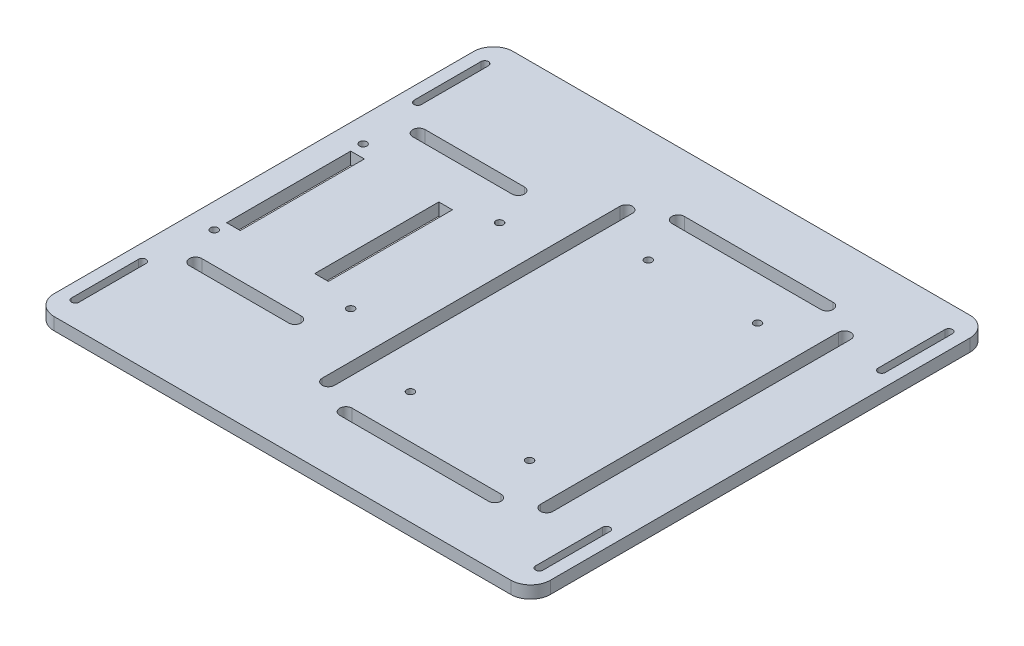
SolidWorks part; units mm, degrees
ref_plane "Front Plane" through (0, 0, 0) normal (0, 0, 1) x (1, 0, 0)
ref_plane "Top Plane" through (0, 0, 0) normal (0, 1, 0) x (1, 0, 0)
ref_plane "Right Plane" through (0, 0, 0) normal (1, 0, 0) x (0, 0, -1)
sketch "Sketch2" plane through (0, 0, 0) normal (0, 1, 0) x (1, 0, 0)
  line L0 (-93.5, 55.5) -> (-93.5, 82.5) construction
  line L1 (-100, -92.5) -> (100, -92.5)
  line L2 (-100, -92.5) -> (-100, 92.5)
  line L3 (-100, 92.5) -> (100, 92.5)
  line L4 (100, -92.5) -> (100, 92.5)
  line L5 (-100, -92.5) -> (100, 92.5) construction
  line L6 (-100, 92.5) -> (100, -92.5) construction
  line L7 (-95, 55.5) -> (-95, 82.5)
  line L8 (-92, 55.5) -> (-92, 82.5)
  line L9 (-100, 0) -> (100, 0) construction
  line L10 (100, 0) -> (0, 92.5) construction
  line L11 (0, 92.5) -> (0, -92.5) construction
  line L12 (93.5, 55.5) -> (93.5, 82.5) construction
  line L13 (95, 55.5) -> (95, 82.5)
  line L14 (92, 55.5) -> (92, 82.5)
  line L15 (93.5, -55.5) -> (93.5, -82.5) construction
  line L16 (95, -55.5) -> (95, -82.5)
  line L17 (92, -55.5) -> (92, -82.5)
  line L18 (-93.5, -55.5) -> (-93.5, -82.5) construction
  line L19 (-95, -55.5) -> (-95, -82.5)
  line L20 (-92, -55.5) -> (-92, -82.5)
  arc A0 (-95, 55.5) -> (-92, 55.5) centre (-93.5, 55.5) ccw
  arc A1 (-92, 82.5) -> (-95, 82.5) centre (-93.5, 82.5) ccw
  arc A2 (95, 55.5) -> (92, 55.5) centre (93.5, 55.5) cw
  arc A3 (92, 82.5) -> (95, 82.5) centre (93.5, 82.5) cw
  arc A4 (95, -55.5) -> (92, -55.5) centre (93.5, -55.5) ccw
  arc A5 (92, -82.5) -> (95, -82.5) centre (93.5, -82.5) ccw
  arc A6 (-95, -55.5) -> (-92, -55.5) centre (-93.5, -55.5) cw
  arc A7 (-92, -82.5) -> (-95, -82.5) centre (-93.5, -82.5) cw
  point P0 (0, 0)
  point P8 (-93.5, 69)
  point P19 (93.5, 69)
  point P26 (93.5, -69)
  point P33 (-93.5, -69)
  dimension "D4" = 1.5
  dimension "D1" = 200
  dimension "D2" = 185
  dimension "D3" = 27
  dimension "D5" = 5
  dimension "D6" = 10
extrude "Boss-Extrude1" add sketch "Sketch2" along normal blind 5
sketch "Sketch3" plane through (0, 5, 0) normal (0, 1, 0) x (1, 0, 0)
  line L0 (-100, 0) -> (100, 0) construction
  line L1 (-100, 92.5) -> (-100, -92.5) construction
  line L2 (100, -92.5) -> (100, 92.5) construction
  line L3 (100, 0) -> (0, -92.5) construction
  line L4 (-100, -92.5) -> (100, -92.5) construction
  line L5 (0, -92.5) -> (0, 92.5) construction
  line L6 (100, 92.5) -> (-100, 92.5) construction
  line L7 (-62.5, -35) -> (-62.5, 55.3864) construction
  line L8 (-30, -35) -> (-95, -35)
  line L9 (-30, -35) -> (-30, 35)
  line L10 (-30, 35) -> (-95, 35)
  line L11 (-95, -35) -> (-95, 35)
  line L12 (-30, -35) -> (-95, 35) construction
  line L13 (-30, 35) -> (-95, -35) construction
  line L14 (-82.5, 45) -> (-42.5, 45) construction
  line L15 (-82.5, 47.5) -> (-42.5, 47.5)
  line L16 (-82.5, 42.5) -> (-42.5, 42.5)
  line L17 (-82.5, -45) -> (-42.5, -45) construction
  line L18 (-82.5, -47.5) -> (-42.5, -47.5)
  line L19 (-82.5, -42.5) -> (-42.5, -42.5)
  line L21 (-90, -25) -> (-84.5, -25)
  line L22 (-90, -25) -> (-90, 25)
  line L23 (-90, 25) -> (-84.5, 25)
  line L24 (-84.5, -25) -> (-84.5, 25)
  line L25 (-90, -25) -> (-84.5, 25) construction
  line L26 (-90, 25) -> (-84.5, -25) construction
  line L27 (-54.5, -25) -> (-49, -25)
  line L28 (-54.5, -25) -> (-54.5, 25)
  line L29 (-54.5, 25) -> (-49, 25)
  line L30 (-49, -25) -> (-49, 25)
  line L31 (-54.5, -25) -> (-49, 25) construction
  line L32 (-54.5, 25) -> (-49, -25) construction
  circle A0 centre (-90, -30) radius 1.5
  circle A1 centre (-90, 30) radius 1.5
  circle A2 centre (-35, 30) radius 1.5
  circle A3 centre (-35, -30) radius 1.5
  arc A4 (-82.5, 47.5) -> (-82.5, 42.5) centre (-82.5, 45) ccw
  arc A5 (-42.5, 42.5) -> (-42.5, 47.5) centre (-42.5, 45) ccw
  arc A6 (-82.5, -47.5) -> (-82.5, -42.5) centre (-82.5, -45) cw
  arc A7 (-42.5, -42.5) -> (-42.5, -47.5) centre (-42.5, -45) cw
  point P9 (-62.5, 0)
  point P29 (-62.5, 45)
  point P36 (-62.5, -45)
  point P41 (-87.25, 0)
  point P46 (-51.75, 0)
  dimension "D4" = 3
  dimension "D8" = 2.5
  dimension "D1" = 65
  dimension "D2" = 70
  dimension "D3" = 5
  dimension "D5" = 5
  dimension "D6" = 5
  dimension "D7" = 40
  dimension "D9" = 10
  dimension "D10" = 5.5
  dimension "D11" = 50
  dimension "D12" = 10
  dimension "D13" = 50
  dimension "D14" = 5.5
  dimension "D15" = 30
extrude "Cut-Extrude1" cut sketch "Sketch3" against normal through all contours L16 A5 L15 A4 | A7 L19 A6 L18 | L21 L24 L23 L22 | L27 L30 L29 L28 | A0 | A1 | A3 | A2 region at (-62.5, 5, -45) region at (-62.5, 5, 45) region at (-87.25, 5, 0) region at (-51.75, 5, 0)
sketch "Sketch4" plane through (0, 5, 0) normal (0, 1, 0) x (1, 0, 0)
  line L0 (-100, 0) -> (100, 0) construction
  line L1 (-100, 92.5) -> (-100, -92.5) construction
  line L2 (100, -92.5) -> (100, 92.5) construction
  line L3 (30, 92.5) -> (30, -92.5) construction
  line L4 (100, 92.5) -> (-100, 92.5) construction
  line L5 (-100, -92.5) -> (100, -92.5) construction
  line L6 (74, -60) -> (74, 60) construction
  line L7 (71.5, -60) -> (71.5, 60)
  line L8 (76.5, -60) -> (76.5, 60)
  line L9 (-14, -60) -> (-14, 60) construction
  line L10 (-16.5, -60) -> (-16.5, 60)
  line L11 (-11.5, -60) -> (-11.5, 60)
  line L12 (0, 66.935) -> (60, 66.935) construction
  line L13 (0, 69.435) -> (60, 69.435)
  line L14 (0, 64.435) -> (60, 64.435)
  line L15 (0, -66.935) -> (60, -66.935) construction
  line L16 (0, -69.435) -> (60, -69.435)
  line L17 (0, -64.435) -> (60, -64.435)
  circle A0 centre (8, 46.935) radius 1.5
  circle A1 centre (52, 46.935) radius 1.5
  circle A2 centre (6, -46.935) radius 1.5
  circle A3 centre (54, -46.935) radius 1.5
  arc A4 (71.5, -60) -> (76.5, -60) centre (74, -60) ccw
  arc A5 (76.5, 60) -> (71.5, 60) centre (74, 60) ccw
  arc A6 (-16.5, -60) -> (-11.5, -60) centre (-14, -60) ccw
  arc A7 (-11.5, 60) -> (-16.5, 60) centre (-14, 60) ccw
  arc A8 (0, 69.435) -> (0, 64.435) centre (0, 66.935) ccw
  arc A9 (60, 64.435) -> (60, 69.435) centre (60, 66.935) ccw
  arc A10 (0, -69.435) -> (0, -64.435) centre (0, -66.935) cw
  arc A11 (60, -64.435) -> (60, -69.435) centre (60, -66.935) cw
  point P22 (74, 0)
  point P29 (-14, 0)
  point P37 (30, 66.935)
  point P44 (30, -66.935)
  dimension "D1" = 3
  dimension "D4" = 3
  dimension "D7" = 46.935
  dimension "D8" = 2.5
  dimension "D12" = 2.5
  dimension "D15" = 2.5
  dimension "D2" = 70
  dimension "D3" = 44
  dimension "D5" = 48
  dimension "D6" = 93.87
  dimension "D9" = 120
  dimension "D10" = 20
  dimension "D11" = 120
  dimension "D13" = 20
  dimension "D14" = 60
  dimension "D16" = 20
extrude "Cut-Extrude3" cut sketch "Sketch4" against normal through all
fillet "Fillet1" radius 8 4 edges at (100, 2.5, -92.5) (100, 2.5, 92.5) (-100, 2.5, -92.5) (-100, 2.5, 92.5)
